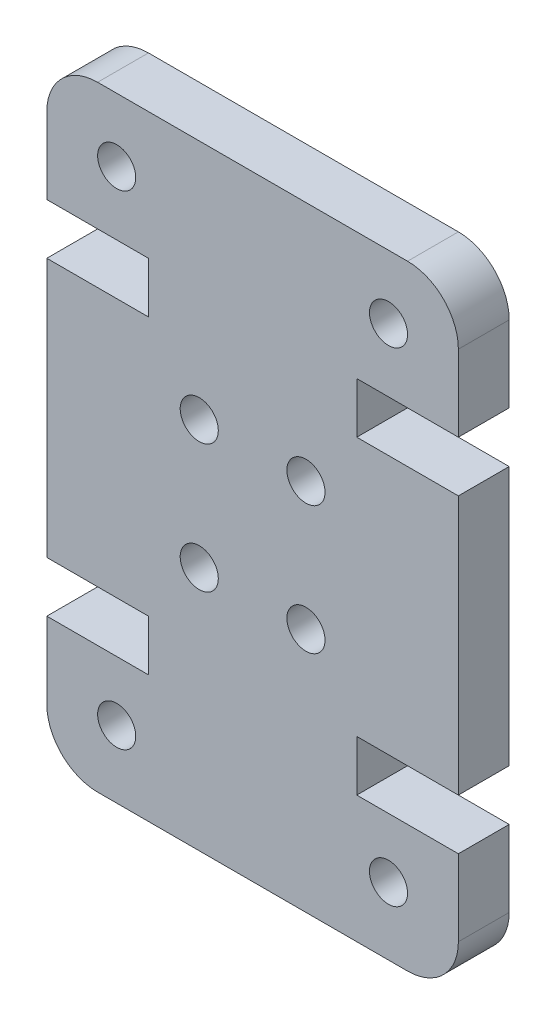
SolidWorks part; units mm, degrees
ref_plane "Front Plane" through (0, 0, 0) normal (0, 0, 1) x (1, 0, 0)
ref_plane "Top Plane" through (0, 0, 0) normal (0, 1, 0) x (1, 0, 0)
ref_plane "Right Plane" through (0, 0, 0) normal (1, 0, 0) x (0, 0, -1)
sketch "Sketch1" plane through (0, 0, 0) normal (0, 0, 1) x (1, 0, 0)
  line L20 (2, 24.2) -> (14.2, 24.2)
  line L21 (2, 0) -> (14.2, 0)
  line L22 (4, 19.2) -> (4, 17.2)
  line L23 (0, 19.2) -> (4, 19.2)
  line L24 (4, 17.2) -> (0, 17.2)
  line L25 (4, 7) -> (4, 5)
  line L26 (0, 22.2) -> (0, 19.2)
  line L27 (16.2, 19.2) -> (16.2, 22.2)
  line L28 (0, 7) -> (4, 7)
  line L29 (12.2, 19.2) -> (12.2, 17.2)
  line L30 (4, 5) -> (0, 5)
  line L31 (12.2, 17.2) -> (16.2, 17.2)
  line L32 (16.2, 19.2) -> (12.2, 19.2)
  line L33 (12.2, 7) -> (12.2, 5)
  line L34 (0, 2) -> (0, 5)
  line L35 (16.2, 5) -> (16.2, 2)
  line L36 (12.2, 5) -> (16.2, 5)
  line L37 (16.2, 7) -> (12.2, 7)
  line L38 (0, 17.2) -> (0, 7)
  line L39 (16.2, 17.2) -> (16.2, 7)
  arc A12 (16.2, 22.2) -> (14.2, 24.2) centre (14.2, 22.2) ccw
  arc A13 (2, 24.2) -> (0, 22.2) centre (2, 22.2) ccw
  circle A14 centre (10.2, 14.7) radius 0.75
  circle A15 centre (6, 14.7) radius 0.75
  arc A16 (14.2, 0) -> (16.2, 2) centre (14.2, 2) ccw
  arc A17 (0, 2) -> (2, 0) centre (2, 2) ccw
  circle A18 centre (10.2, 9.6536) radius 0.75
  circle A19 centre (6, 9.6536) radius 0.75
  circle A20 centre (13.45, 2.6536) radius 0.75
  circle A21 centre (2.75, 2.6536) radius 0.75
  circle A22 centre (13.45, 21.7) radius 0.75
  circle A23 centre (2.75, 21.7) radius 0.75
extrude "Boss-Extrude1" add sketch "Sketch1" along normal blind 2
